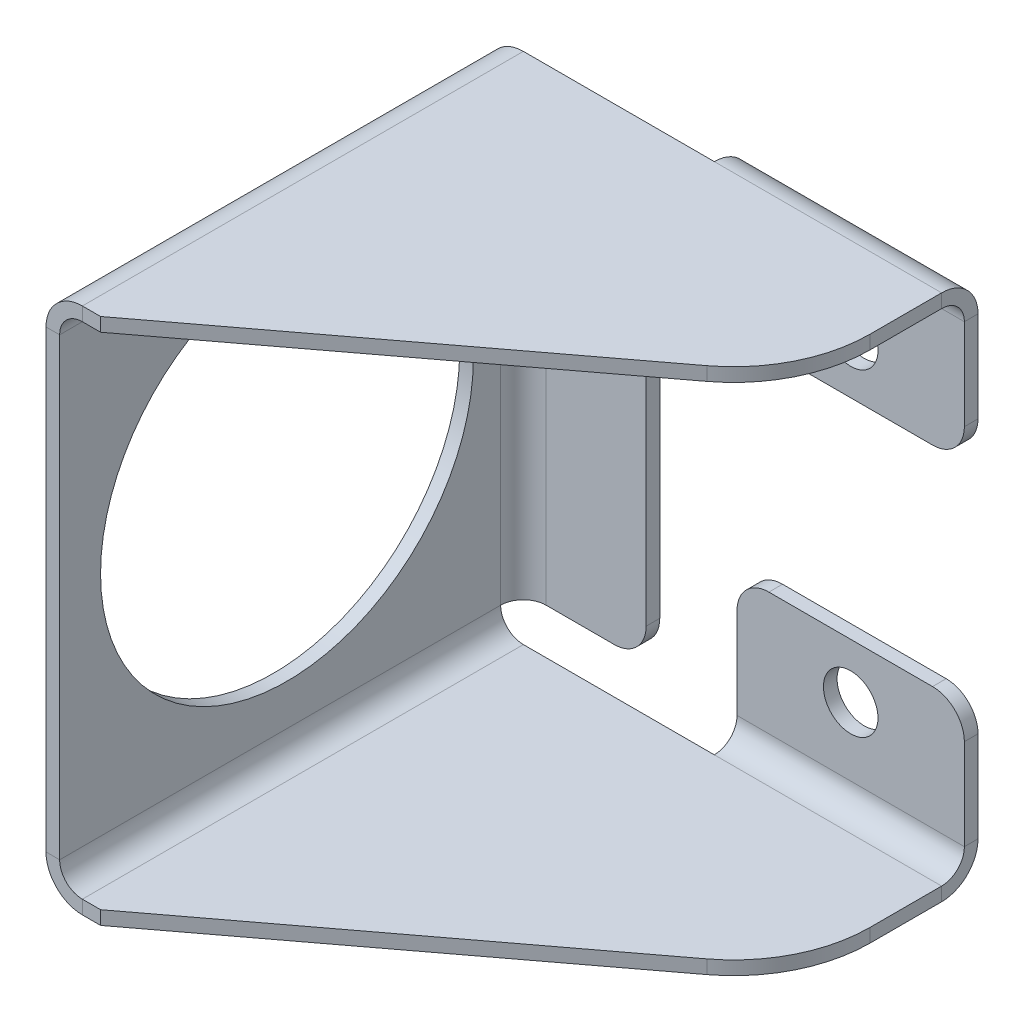
SolidWorks part; units mm, degrees
note: The reader was unsure of these and kept them because the rebuilt part matched: flange length of "Edge-Flange1", "Edge-Flange2", "Edge-Flange3".
material "Plain Carbon Steel"
ref_plane "Front Plane" through (0, 0, 0) normal (1, 0, 0) x (0, 1, 0)
ref_plane "Top Plane" through (0, 0, 0) normal (0, 0, 1) x (0, 1, 0)
ref_plane "Right Plane" through (0, 0, 0) normal (0, 1, 0) x (-1, 0, 0)
sketch "Sketch1" plane through (0, 0, 0) normal (0, 0, 1) x (0, 1, 0)
  line L1 (-50, 15) -> (50, 15)
  line L2 (-50, 15) -> (-50, -15)
  line L3 (-50, -15) -> (50, -15)
  line L4 (50, 15) -> (50, -15)
  line L5 (-50, 15) -> (50, -15) construction
  line L6 (-50, -15) -> (50, 15) construction
  point P0 (0, 0)
  dimension "D1" = 100
  dimension "D2" = 30
base flange "Base-Flange1" sketch "Sketch1" thickness 3 reverse thickness direction yes parameters "D1"=5
edge flange "Edge-Flange1" sketch "Sketch8" flange angle 90 flange length 105 flange position material inside bend radius 5 thickness 3 relief rectangular parameters "D6"=10
sketch "Sketch8" plane through (-15, 0, 3) normal (-1, 0, 0) x (0, -1, 0)
  line L2 (-50, 0) -> (-50, 102)
  line L3 (-50, 102) -> (50, 102)
  line L4 (50, 102) -> (50, 0)
  line L7 (-50, 0) -> (50, 0) construction
  line L8 (-50, 0) -> (50, 0)
  line L9 (-50, -3) -> (50, -3) construction
  dimension "D1" = 105
bend "EdgeBend1" bend radius 5 bend angle 90 parameters "D5"=1
edge flange "Edge-Flange2" sketch "Sketch12" flange angle 90 flange length 100 flange position bend outside bend radius 5 thickness 3 relief rectangular parameters "D6"=10
sketch "Sketch12" plane through (-12, 50, 0) normal (0, 1, 0) x (0, 0, 1)
  line L2 (8, 0) -> (8, 97)
  line L3 (8, 97) -> (23.7298, 97)
  line L11 (105, 0) -> (8, 0) construction
  line L12 (105, 0) -> (8, 0)
  line L13 (105, -3) -> (8, -3) construction
  line L15 (105, 0) -> (105, 9)
  line L16 (105, 9) -> (47.6889, 85.0545)
  arc A0 (23.7298, 97) -> (47.6889, 85.0545) centre (23.7298, 67) cw
  dimension "D2" = 30
  dimension "D4" = 37
  dimension "D1" = 12
  dimension "D3" = 100
bend "EdgeBend2" bend radius 5 bend angle 90 parameters "D5"=2
edge flange "Edge-Flange3" sketch "Sketch15" flange angle 90 flange length 35 flange position bend outside bend radius 5 thickness 3 relief rectangular parameters "D6"=10
sketch "Sketch15" plane through (0, 55, 8) normal (0, 0, -1) x (1, 0, 0)
  line L2 (35, 0) -> (35, 32)
  line L3 (35, 32) -> (85, 32)
  line L4 (85, 32) -> (85, 0)
  line L7 (85, 0) -> (-7, 0) construction
  line L8 (85, 0) -> (35, 0)
  line L10 (85, -3) -> (-7, -3) construction
  dimension "D1" = 50
  dimension "D2" = 35
bend "EdgeBend3" bend radius 5 bend angle 90 parameters "D5"=3
sketch "Sketch16" plane through (0, 0, 3) normal (0, 0, 1) x (1, 0, 0)
  line L0 (85, 50) -> (85, 23) construction
  circle A0 centre (60, 35) radius 6
  dimension "D1" = 12
  dimension "D2" = 35
  dimension "D3" = 25
extrude "Cut-Extrude1" cut sketch "Sketch16" against normal blind 10
sketch "Sketch17" plane through (-15, 0, 0) normal (-1, 0, 0) x (0, -1, 0)
  line L0 (50, 105) -> (-50, 105) construction
  circle A0 centre (0, 55) radius 41
  dimension "D1" = 82
  dimension "D2" = 50
extrude "Cut-Extrude2" cut sketch "Sketch17" against normal blind 10
fillet "Fillet1" radius 7 3 edges at (85, 23, 1.5) (35, 23, 1.5) (15, 50, 1.5)
other "SurfaceCut1"
mirror "Mirror2" about plane through (0, 0, 0) normal (0, 1, 0) of bodies 107
bend "MirrorBend3" bend radius 5 bend angle 90 parameters "D5"=4
bend "MirrorBend4" bend radius 5 bend angle 90 parameters "D5"=5
other "SurfaceCut2"
mirror "Mirror3" about plane through (0, 0, 0) normal (0, 1, 0) of bodies 110
bend "MirrorBend5" bend radius 5 bend angle 90 parameters "D5"=4
bend "MirrorBend6" bend radius 5 bend angle 90 parameters "D5"=5
sketch "Bend-Lines1" [suppressed] plane through (0, 0, 0) normal (0, 1, 0) x (1, 0, 0)
sketch "Bounding-Box1" [suppressed] plane through (0, 0, 0) normal (0, 1, 0) x (1, 0, 0)
sheet metal parameters "Sheet-Metal1" thickness 3 parameters "D1"=5
flat pattern "Flat-Pattern1" [suppressed]
sketch "Bend-Lines2" plane through (0, 0, 0) normal (0, 1, 0) x (1, 0, 0)
sketch3d "Bounding-Box2" [suppressed]
  line L0 (15, 50, 0) -> (15, -50, 0) construction
  line L1 (-15, 50, 0) -> (-15, -50, 0) construction
  line L2 (15, 50, 0) -> (-15, 50, 0) construction
  line L3 (15, -50, 0) -> (-15, -50, 0) construction
sheet metal parameters "Sheet-Metal2" thickness 3 parameters "D1"=5
flat pattern "Flat-Pattern1"
sketch "Bend-Lines2" plane through (0, 0, 3) normal (0, 0, 1) x (1, 0, 0)
  line L0 (-12.1051, -50) -> (-12.1051, 50) construction
  line L1 (-12.1051, -50) -> (-12.1051, 50) construction
sketch3d "Bounding-Box2" [suppressed]
  line L0 (-114.2102, -50, 0) -> (15, -50, 0) construction
  line L1 (-114.2102, 50, 0) -> (15, 50, 0) construction
  line L2 (-114.2102, -50, 0) -> (-114.2102, 50, 0) construction
  line L3 (15, -50, 0) -> (15, 50, 0) construction
bend of the flat pattern "Flatten-<EdgeBend1>1"
sheet metal parameters "Sheet-Metal3" thickness 3 parameters "D1"=5
flat pattern "Flat-Pattern1"
sketch "Bend-Lines2" plane through (0, 0, 3) normal (0, 0, 1) x (1, 0, 0)
  line L0 (-12.1051, -50) -> (-12.1051, 50) construction
  line L1 (-12.1051, -50) -> (-12.1051, 50) construction
  line L2 (-114.2102, 55.1051) -> (-17.2102, 55.1051) construction
  line L3 (-114.2102, 55.1051) -> (-17.2102, 55.1051) construction
sketch3d "Bounding-Box2" [suppressed]
  line L0 (15, 152.2102, 0) -> (15, -50, 0) construction
  line L1 (-114.2102, 152.2102, 0) -> (-114.2102, -50, 0) construction
  line L2 (15, 152.2102, 0) -> (-114.2102, 152.2102, 0) construction
  line L3 (15, -50, 0) -> (-114.2102, -50, 0) construction
bend of the flat pattern "Flatten-<EdgeBend1>1"
bend of the flat pattern "Flatten-<EdgeBend2>1"
sheet metal parameters "Sheet-Metal4" thickness 3 parameters "D1"=5
flat pattern "Flat-Pattern1"
sketch "Bend-Lines2" plane through (0, 0, 3) normal (0, 0, 1) x (1, 0, 0)
  line L0 (-12.1051, -50) -> (-12.1051, 50) construction
  line L1 (-12.1051, -50) -> (-12.1051, 50) construction
  line L2 (-114.2102, 55.1051) -> (-17.2102, 55.1051) construction
  line L3 (-114.2102, 55.1051) -> (-17.2102, 55.1051) construction
  line L4 (-12.1051, 152.2102) -> (-12.1051, 102.2102) construction
  line L5 (-12.1051, 152.2102) -> (-12.1051, 102.2102) construction
sketch3d "Bounding-Box2" [suppressed]
  line L0 (20, 152.2102, 0) -> (20, -50, 0) construction
  line L1 (-114.2102, 152.2102, 0) -> (-114.2102, -50, 0) construction
  line L2 (20, 152.2102, 0) -> (-114.2102, 152.2102, 0) construction
  line L3 (20, -50, 0) -> (-114.2102, -50, 0) construction
bend of the flat pattern "Flatten-<EdgeBend1>1"
bend of the flat pattern "Flatten-<EdgeBend2>1"
bend of the flat pattern "Flatten-<EdgeBend3>1"
sheet metal parameters "Sheet-Metal5" thickness 3 parameters "D1"=5
flat pattern "Flat-Pattern1"
sketch "Bend-Lines2" plane through (0, 0, 3) normal (0, 0, 1) x (1, 0, 0)
  line L0 (-12.1051, -50) -> (-12.1051, 50) construction
  line L1 (-12.1051, -50) -> (-12.1051, 50) construction
  line L2 (-114.2102, 55.1051) -> (-17.2102, 55.1051) construction
  line L3 (-114.2102, 55.1051) -> (-17.2102, 55.1051) construction
  line L4 (-12.1051, 152.2102) -> (-12.1051, 102.2102) construction
  line L5 (-12.1051, 152.2102) -> (-12.1051, 102.2102) construction
sketch3d "Bounding-Box2" [suppressed]
  line L0 (20, 152.2102, 0) -> (20, -50, 0) construction
  line L1 (-114.2102, 152.2102, 0) -> (-114.2102, -50, 0) construction
  line L2 (20, 152.2102, 0) -> (-114.2102, 152.2102, 0) construction
  line L3 (20, -50, 0) -> (-114.2102, -50, 0) construction
bend of the flat pattern "Flatten-<EdgeBend1>1"
bend of the flat pattern "Flatten-<EdgeBend2>1"
bend of the flat pattern "Flatten-<EdgeBend3>1"
sheet metal parameters "Sheet-Metal6" thickness 3 parameters "D1"=5
flat pattern "Flat-Pattern1"
sketch "Bend-Lines2" plane through (0, 0, 3) normal (0, 0, 1) x (1, 0, 0)
  line L0 (-12.1051, -50) -> (-12.1051, 50) construction
  line L1 (-12.1051, -50) -> (-12.1051, 50) construction
  line L2 (-114.2102, 55.1051) -> (-17.2102, 55.1051) construction
  line L3 (-114.2102, 55.1051) -> (-17.2102, 55.1051) construction
  line L4 (-12.1051, 152.2102) -> (-12.1051, 102.2102) construction
  line L5 (-12.1051, 152.2102) -> (-12.1051, 102.2102) construction
sketch3d "Bounding-Box2" [suppressed]
  line L0 (20, -50, 0) -> (20, 152.2102, 0) construction
  line L1 (-114.2102, -50, 0) -> (-114.2101, 152.2102, 0) construction
  line L2 (20, -50, 0) -> (-114.2102, -50, 0) construction
  line L3 (20, 152.2102, 0) -> (-114.2101, 152.2102, 0) construction
bend of the flat pattern "Flatten-<EdgeBend1>1"
bend of the flat pattern "Flatten-<EdgeBend2>1"
bend of the flat pattern "Flatten-<EdgeBend3>1"
sheet metal parameters "Sheet-Metal7" thickness 3 parameters "D1"=5
flat pattern "Flat-Pattern1"
sketch "Bend-Lines2" plane through (0, 0, 3) normal (0, 0, 1) x (1, 0, 0)
  line L0 (-12.1051, 0) -> (-12.1051, 50) construction
  line L1 (-12.1051, 0) -> (-12.1051, 50) construction
  line L2 (-114.2102, 55.1051) -> (-17.2102, 55.1051) construction
  line L3 (-114.2102, 55.1051) -> (-17.2102, 55.1051) construction
  line L4 (-12.1051, 152.2102) -> (-12.1051, 102.2102) construction
  line L5 (-12.1051, 152.2102) -> (-12.1051, 102.2102) construction
sketch3d "Bounding-Box2" [suppressed]
  line L0 (20, 0, 0) -> (20, 152.2102, 0) construction
  line L1 (-114.2102, 0, 0) -> (-114.2102, 152.2102, 0) construction
  line L2 (20, 0, 0) -> (-114.2102, 0, 0) construction
  line L3 (20, 152.2102, 0) -> (-114.2102, 152.2102, 0) construction
bend of the flat pattern "Flatten-<EdgeBend1>1"
bend of the flat pattern "Flatten-<EdgeBend2>1"
bend of the flat pattern "Flatten-<EdgeBend3>1"
sheet metal parameters "Sheet-Metal9" thickness 3 parameters "D1"=5
flat pattern "Flat-Pattern9"
sketch "Bend-Lines4" plane through (0, 0, 3) normal (0, 0, 1) x (1, 0, 0)
  line L0 (-12.1051, -102.2102) -> (-12.1051, -152.2102) construction
  line L1 (-17.2102, -55.1051) -> (-114.2102, -55.1051) construction
  line L2 (-12.1051, 152.2102) -> (-12.1051, 102.2102) construction
  line L3 (-114.2102, 55.1051) -> (-17.2102, 55.1051) construction
  line L4 (-12.1051, -50) -> (-12.1051, 50) construction
  line L5 (-12.1051, -102.2102) -> (-12.1051, -152.2102) construction
  line L6 (-17.2102, -55.1051) -> (-114.2102, -55.1051) construction
  line L7 (-12.1051, 152.2102) -> (-12.1051, 102.2102) construction
  line L8 (-114.2102, 55.1051) -> (-17.2102, 55.1051) construction
  line L9 (-12.1051, -50) -> (-12.1051, 50) construction
sketch3d "Bounding-Box4" [suppressed]
  line L0 (20, -152.2102, 0) -> (20, 152.2102, 0) construction
  line L1 (-114.2102, -152.2102, 0) -> (-114.2102, 152.2102, 0) construction
  line L2 (20, -152.2102, 0) -> (-114.2102, -152.2102, 0) construction
  line L3 (20, 152.2102, 0) -> (-114.2102, 152.2102, 0) construction
bend of the flat pattern "Flatten-<EdgeBend3>3"
bend of the flat pattern "Flatten-<EdgeBend2>3"
bend of the flat pattern "Flatten-<EdgeBend1>3"
bend of the flat pattern "Flatten-<MirrorBend3>1"
bend of the flat pattern "Flatten-<MirrorBend4>1"
sheet metal parameters "Sheet-Metal10" thickness 3 parameters "D1"=5
flat pattern "Flat-Pattern9"
sketch "Bend-Lines4" plane through (0, 0, 3) normal (0, 0, 1) x (1, 0, 0)
  line L2 (-12.1051, 152.2102) -> (-12.1051, 102.2102) construction
  line L3 (-114.2102, 55.1051) -> (-17.2102, 55.1051) construction
  line L4 (-12.1051, 0) -> (-12.1051, 50) construction
  line L7 (-12.1051, 152.2102) -> (-12.1051, 102.2102) construction
  line L8 (-114.2102, 55.1051) -> (-17.2102, 55.1051) construction
  line L9 (-12.1051, 0) -> (-12.1051, 50) construction
sketch3d "Bounding-Box4" [suppressed]
  line L0 (20, 0, 0) -> (20, 152.2102, 0) construction
  line L1 (-114.2102, 0, 0) -> (-114.2102, 152.2102, 0) construction
  line L2 (20, 0, 0) -> (-114.2102, 0, 0) construction
  line L3 (20, 152.2102, 0) -> (-114.2102, 152.2102, 0) construction
bend of the flat pattern "Flatten-<EdgeBend3>3"
bend of the flat pattern "Flatten-<EdgeBend2>3"
bend of the flat pattern "Flatten-<EdgeBend1>3"
sheet metal parameters "Sheet-Metal11" thickness 3 parameters "D1"=5
flat pattern "Flat-Pattern11"
sketch "Bend-Lines5" plane through (0, 0, 3) normal (0, 0, 1) x (1, 0, 0)
  line L0 (-12.1051, -102.2102) -> (-12.1051, -152.2102) construction
  line L1 (-17.2102, -55.1051) -> (-114.2102, -55.1051) construction
  line L2 (-12.1051, 152.2102) -> (-12.1051, 102.2102) construction
  line L3 (-114.2102, 55.1051) -> (-17.2102, 55.1051) construction
  line L4 (-12.1051, -50) -> (-12.1051, 50) construction
  line L5 (-12.1051, -102.2102) -> (-12.1051, -152.2102) construction
  line L6 (-17.2102, -55.1051) -> (-114.2102, -55.1051) construction
  line L7 (-12.1051, 152.2102) -> (-12.1051, 102.2102) construction
  line L8 (-114.2102, 55.1051) -> (-17.2102, 55.1051) construction
  line L9 (-12.1051, -50) -> (-12.1051, 50) construction
sketch3d "Bounding-Box5" [suppressed]
  line L0 (20, -152.2102, 0) -> (20, 152.2102, 0) construction
  line L1 (-114.2102, -152.2102, 0) -> (-114.2102, 152.2102, 0) construction
  line L2 (20, -152.2102, 0) -> (-114.2102, -152.2102, 0) construction
  line L3 (20, 152.2102, 0) -> (-114.2102, 152.2102, 0) construction
bend of the flat pattern "Flatten-<EdgeBend3>4"
bend of the flat pattern "Flatten-<EdgeBend2>4"
bend of the flat pattern "Flatten-<EdgeBend1>4"
bend of the flat pattern "Flatten-<MirrorBend5>1"
bend of the flat pattern "Flatten-<MirrorBend6>1"
